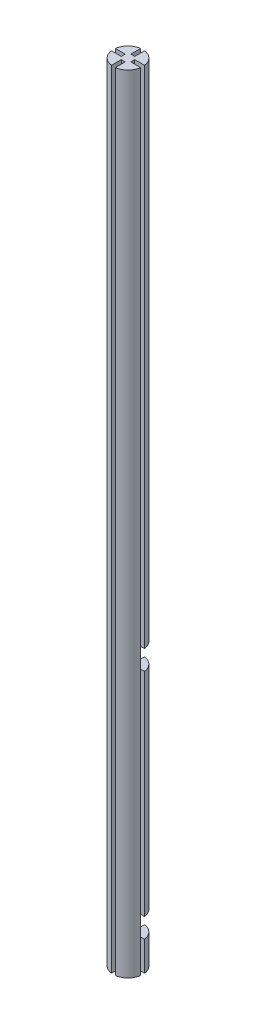
SolidWorks part; units mm, degrees
ref_plane "Front Plane" through (0, 0, 0) normal (0, 0, 1) x (1, 0, 0)
ref_plane "Top Plane" through (0, 0, 0) normal (0, 1, 0) x (1, 0, 0)
ref_plane "Right Plane" through (0, 0, 0) normal (1, 0, 0) x (0, 0, -1)
sketch "Sketch1" plane through (0, 0, 0) normal (0, 1, 0) x (1, 0, 0)
  line L5 (0, 194.153) -> (0, -244.4898) construction
  line L18 (-10, 74.3303) -> (-10, 24.3303)
  line L19 (-10, 24.3303) -> (10, 24.3303)
  line L20 (10, 74.3303) -> (10, 24.3303)
  line L21 (-29.2048, 0) -> (25.2155, 0) construction
  line L22 (74.3303, -10) -> (24.3303, -10)
  line L23 (74.3303, 10) -> (24.3303, 10)
  line L24 (24.3303, 10) -> (24.3303, -10)
  line L25 (-10, -74.3303) -> (-10, -24.3303)
  line L26 (10, -74.3303) -> (10, -24.3303)
  line L27 (10, -24.3303) -> (-10, -24.3303)
  line L28 (-74.3303, 10) -> (-24.3303, 10)
  line L29 (-74.3303, -10) -> (-24.3303, -10)
  line L30 (-24.3303, -10) -> (-24.3303, 10)
  arc A2 (-10, 74.3303) -> (-74.3303, 10) centre (0, 0) ccw
  arc A3 (-74.3303, -10) -> (-10, -74.3303) centre (0, 0) ccw
  arc A4 (10, -74.3303) -> (74.3303, -10) centre (0, 0) ccw
  arc A5 (74.3303, 10) -> (10, 74.3303) centre (0, 0) ccw
  point P1 (0, 24.3303)
  point P4 (0, 93.7498)
  point P24 (-100, 0)
  point P29 (0, 0)
  point P30 (0, 0)
  dimension "D1" = 150
  dimension "D2" = 20
  dimension "D3" = 50
  dimension "D4" = 4
extrude "Boss-Extrude2" add sketch "Sketch1" along normal blind 4000 contours A2 L28 L30 L29 A3 L25 L27 L26 A4 L22 L24 L23 A5 L20 L19 L18
sketch "Sketch2" plane through (0, 0, 0) normal (0, 1, 0) x (1, 0, 0)
  line L0 (0, 74.3303) -> (0, 0)
  line L1 (74.3303, 74.3303) -> (74.3303, 0)
  line L2 (74.3303, 74.3303) -> (0, 74.3303)
  line L3 (74.3303, 0) -> (0, 0)
extrude "Cut-Extrude1" cut sketch "Sketch2" along normal mid plane 100 from offset 200
extrude "Cut-Extrude2" cut sketch "Sketch2<2>" against normal mid plane 100 from offset 1380
sketch "Sketch2<2>" plane through (0, 0, 0) normal (0, 1, 0) x (1, 0, 0) same geometry as "Sketch2"
